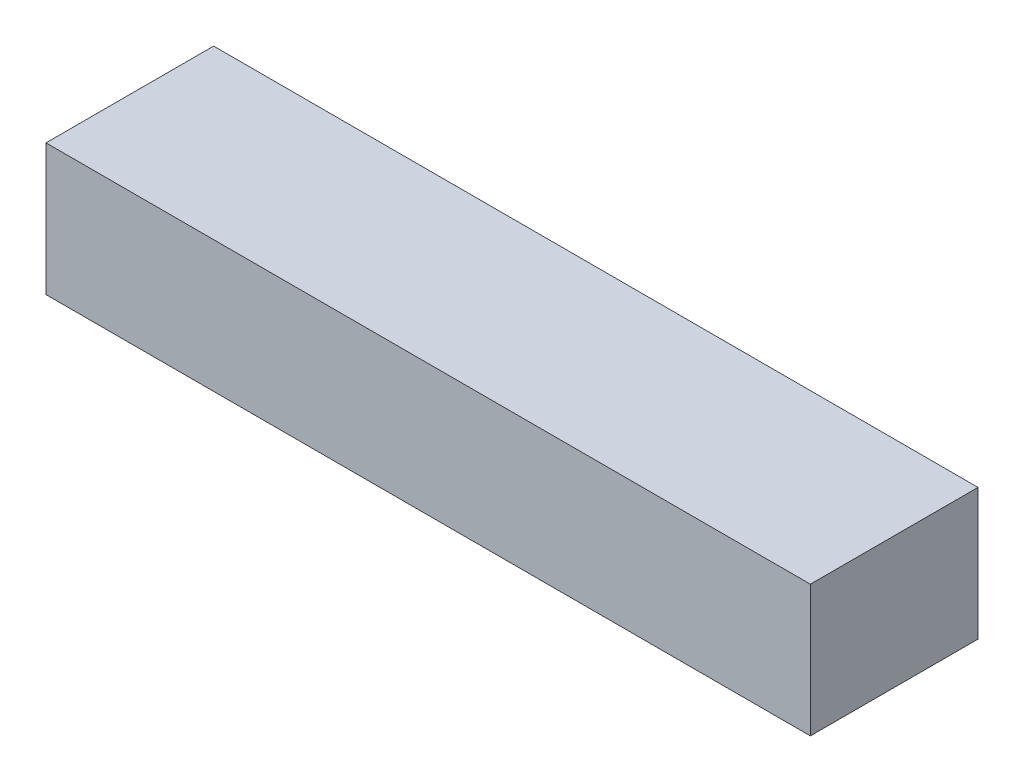
SolidWorks part; units mm, degrees
ref_plane "Front Plane" through (0, 0, 0) normal (0, 0, 1) x (1, 0, 0)
ref_plane "Top Plane" through (0, 0, 0) normal (0, 1, 0) x (1, 0, 0)
ref_plane "Right Plane" through (0, 0, 0) normal (1, 0, 0) x (0, 0, -1)
sketch "Sketch1" plane through (0, 0, 0) normal (0, 1, 0) x (1, 0, 0)
  line L1 (570, -125) -> (-570, -125)
  line L2 (570, -125) -> (570, 125)
  line L3 (570, 125) -> (-570, 125)
  line L4 (-570, -125) -> (-570, 125)
  line L5 (570, -125) -> (-570, 125) construction
  line L6 (570, 125) -> (-570, -125) construction
  point P0 (0, 0)
  dimension "D1" = 1140
  dimension "D2" = 250
extrude "Boss-Extrude1" add sketch "Sketch1" along normal blind 196
equation "\"assembly\" = 0"
equation "\"thickness 1\" = 3"
equation "\"thickness 2\" = 8"
equation "\"connecting flange\" = 35"
equation "\"main\" = 0"
equation "\"main length\" = 1200"
equation "\"main width\" = 1200"
equation "\"divider panel distance offset\" = 250"
equation "\"side panel\" = 0"
equation "\"access hatch length\" = 600"
equation "\"access hatch width\" = 450"
equation "\"access hatch offset X\" = 100"
equation "\"access hatch offset Y\" = 100"
equation "\"side panel length\" = 1200"
equation "\"side panel width\" = 1000"
equation "\"back panel\" = 0"
equation "\"back panel access hatch length\" = 1150"
equation "\"back panel access hatch width\" = 206"
equation "\"back panel access hatch flange\" = 40"
equation "\"drift eliminator\" = 0"
equation "\"drift eliminator size offset\" = 10"
equation "\"drift eliminator length\" = \"back panel access hatch length\" - \"drift eliminator size offset\""
equation "\"drift eliminator width\" = \"back panel access hatch width\" - \"drift eliminator size offset\""
equation "\"drift eliminator depth\" = \"divider panel distance offset\""
equation "\"sump\" = 0"
equation "\"D1@Boss-Extrude1\"=\"drift eliminator width\""
equation "\"D1@Sketch1\"=\"drift eliminator length\""
equation "\"D2@Sketch1\"=\"drift eliminator depth\""
